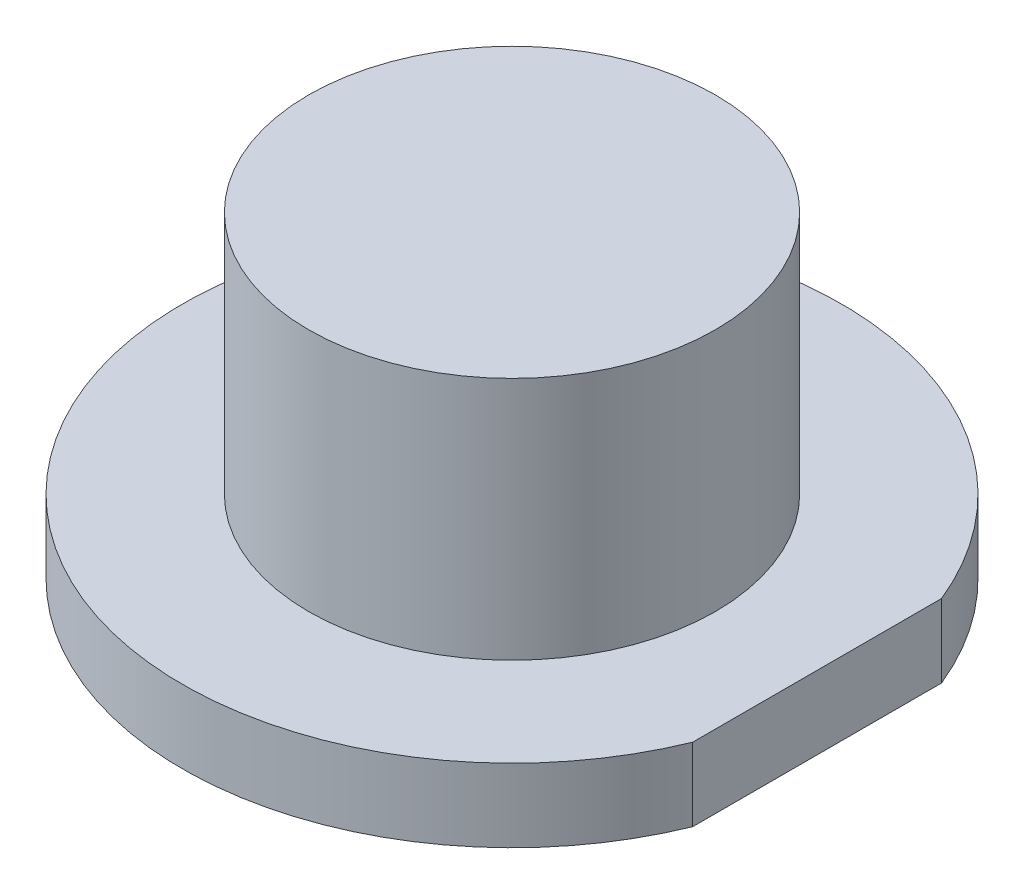
SolidWorks part; units mm, degrees
material "PE High Density"
ref_plane "Front Plane" through (0, 0, 0) normal (0, 0, 1) x (1, 0, 0)
ref_plane "Top Plane" through (0, 0, 0) normal (0, 1, 0) x (1, 0, 0)
ref_plane "Right Plane" through (0, 0, 0) normal (1, 0, 0) x (0, 0, -1)
sketch "Sketch1" plane through (0, 0, 0) normal (0, 1, 0) x (1, 0, 0)
  circle A0 centre (0, 0) radius 4.05
  dimension "D1" = 8.1
extrude "Boss-Extrude1" add sketch "Sketch1" along normal blind 0.9
sketch "Sketch2" plane through (0, 0.9, 0) normal (0, 1, 0) x (1, 0, 0)
  line L0 (-4.05, 0) -> (3.75, 0)
  line L1 (3.75, 1.5297) -> (3.75, -1.5297)
  circle A0 centre (0, 0) radius 4.05 construction
  arc A1 (3.75, 1.5297) -> (3.75, -1.5297) centre (0, 0) cw
  circle M2 centre (0, 0) radius 4.05
  dimension "D1" = 7.8
extrude "Cut-Extrude1" cut sketch "Sketch2" against normal blind 0.9 contours L1 M2 region at (3.8704, 0.9, 0)
sketch "Sketch3" plane through (0, 0.9, 0) normal (0, 1, 0) x (1, 0, 0)
  circle A0 centre (0, 0) radius 2.5
  dimension "D1" = 5
extrude "Boss-Extrude2" add sketch "Sketch3" along normal blind 3
sketch "Sketch4" plane through (0, 0, 0) normal (0, -1, 0) x (1, 0, 0)
  line L0 (-0.25, 0.25) -> (-1.9843, 0.25)
  line L1 (0.25, -0.25) -> (-0.25, -0.25)
  line L2 (0.25, -0.25) -> (0.25, 0.25)
  line L3 (0.25, 0.25) -> (-0.25, 0.25)
  line L4 (-0.25, -0.25) -> (-0.25, 0.25)
  line L5 (0.25, -0.25) -> (-0.25, 0.25) construction
  line L6 (0.25, 0.25) -> (-0.25, -0.25) construction
  line L7 (-0.25, -0.25) -> (-1.9843, -0.25)
  line L8 (-0.25, 0.25) -> (-0.25, 1.9843)
  line L9 (0.25, 0.25) -> (0.25, 1.9843)
  line L10 (0.25, 0.25) -> (1.9843, 0.25)
  line L11 (-0.25, -0.25) -> (-0.25, -1.9843)
  line L12 (0.25, -0.25) -> (0.25, -1.9843)
  line L13 (0.25, -0.25) -> (1.9843, -0.25)
  circle A0 centre (0, 0) radius 2
  dimension "D1" = 4
  dimension "D2" = 0.5
  dimension "D3" = 0.5
extrude "Cut-Extrude3" cut sketch "Sketch4" against normal blind 2.5 contours L8 A0 L0 | L10 A0 L9 | L7 A0 L11 region at (-0.9584, 0, 0.9584) region at (0.9584, 0, 0.9584) region at (-0.9584, 0, -0.9584)
extrude "Cut-Extrude4" cut sketch "Sketch4<3>" against normal blind 0.25 contours L12 A0 L13 region at (0.9584, 0, -0.9584)
sketch "Sketch4<3>" plane through (0, 0, 0) normal (0, -1, 0) x (1, 0, 0) same geometry as "Sketch4"
